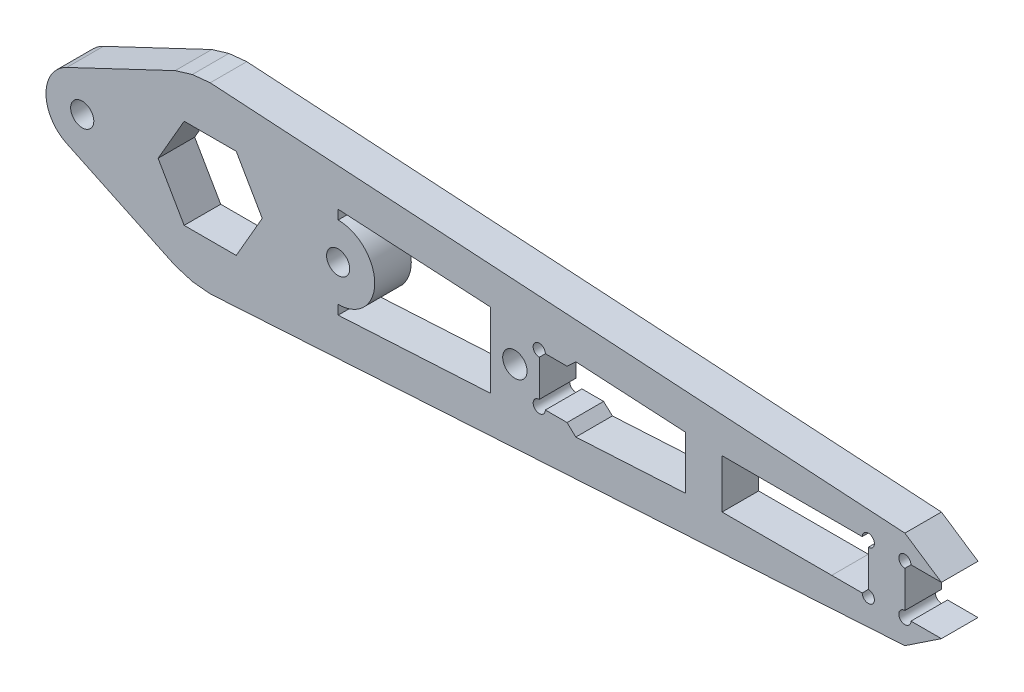
SolidWorks part; units mm, degrees
ref_plane "前视基准面" through (0, 0, 0) normal (0, 0, 1) x (1, 0, 0)
ref_plane "上视基准面" through (0, 0, 0) normal (0, 1, 0) x (1, 0, 0)
ref_plane "右视基准面" through (0, 0, 0) normal (1, 0, 0) x (0, 0, -1)
sketch "草图2" plane through (0, 0, 0) normal (0, 0, 1) x (1, 0, 0)
  line L0 (42, 2.0029) -> (51, 2)
  line L1 (51, 2) -> (53.5, 2)
  line L2 (42, -2.0029) -> (51, -2)
  line L3 (51, -2) -> (53.5, -2)
  line L4 (57, 4) -> (0, 7.5)
  line L5 (0, 7.5) -> (-1.4632, 7.3559)
  line L6 (-1.4632, 7.3559) -> (-2.8701, 6.9291)
  line L7 (-2.8701, 6.9291) -> (-11.763, 2.7105)
  line L8 (-11.763, -2.7105) -> (-2.8701, -6.9291)
  line L9 (-2.8701, -6.9291) -> (-1.4632, -7.3559)
  line L10 (-1.4632, -7.3559) -> (0, -7.5)
  line L11 (0, -7.5) -> (57, -4)
  line L12 (27.5, 2) -> (29.2826, 2)
  line L13 (27, -1.5) -> (27, 1.5)
  line L14 (29.2826, -2) -> (30, -2.6735)
  line L15 (30, -2.6735) -> (39, -2.1706)
  line L16 (39, 2.1706) -> (39, -2.1706)
  line L17 (30, 2.6735) -> (39, 2.1706)
  line L18 (30, 2.6735) -> (29.2826, 2)
  line L19 (10.5, -3.7632) -> (10.5, -3)
  line L20 (10.5, -3.7632) -> (23, -3.0647)
  line L21 (23, 3.0647) -> (23, -3.0647)
  line L22 (10.5, 3.7632) -> (23, 3.0647)
  line L23 (10.5, 3.7632) -> (10.5, 3)
  line L24 (-4.2724, 0) -> (-2.1362, 3.7)
  line L25 (-2.1362, -3.7) -> (-4.2724, 0)
  line L26 (2.1362, -3.7) -> (-2.1362, -3.7)
  line L27 (4.2724, 0) -> (2.1362, -3.7)
  line L28 (2.1362, 3.7) -> (4.2724, 0)
  line L29 (-2.1362, 3.7) -> (2.1362, 3.7)
  line L30 (42, -2.0029) -> (42, 2.0029)
  line L31 (54, 1.5) -> (54, -1.5)
  line L32 (57, -4) -> (60, -2)
  line L33 (57, -1.5) -> (57, 1.5)
  line L34 (57, 4) -> (60, 2)
  line L35 (57.5, -2) -> (60, -2)
  line L36 (60, 2) -> (57.5, 2)
  line L37 (29.2826, -2) -> (27.5, -2)
  circle A0 centre (25, 0) radius 1
  circle A1 centre (10.5, 0) radius 0.95
  circle A2 centre (-10.5, 0) radius 0.95
  arc A3 (-11.763, 2.7105) -> (-11.763, -2.7105) centre (-10.4772, 0) ccw
  arc A4 (27.5, 2) -> (27, 1.5) centre (27, 2) ccw
  arc A5 (27, -1.5) -> (27.5, -2) centre (27, -2) ccw
  arc A6 (10.5, -3) -> (10.5, 3) centre (10.5, 0) ccw
  arc A7 (53.5, -2) -> (54, -1.5) centre (54, -2) ccw
  arc A8 (54, 1.5) -> (53.5, 2) centre (54, 2) ccw
  arc A9 (57, -1.5) -> (57.5, -2) centre (57, -2) ccw
  arc A10 (57.5, 2) -> (57, 1.5) centre (57, 2) ccw
extrude "凸台-拉伸2" add sketch "草图2" along normal blind 3
